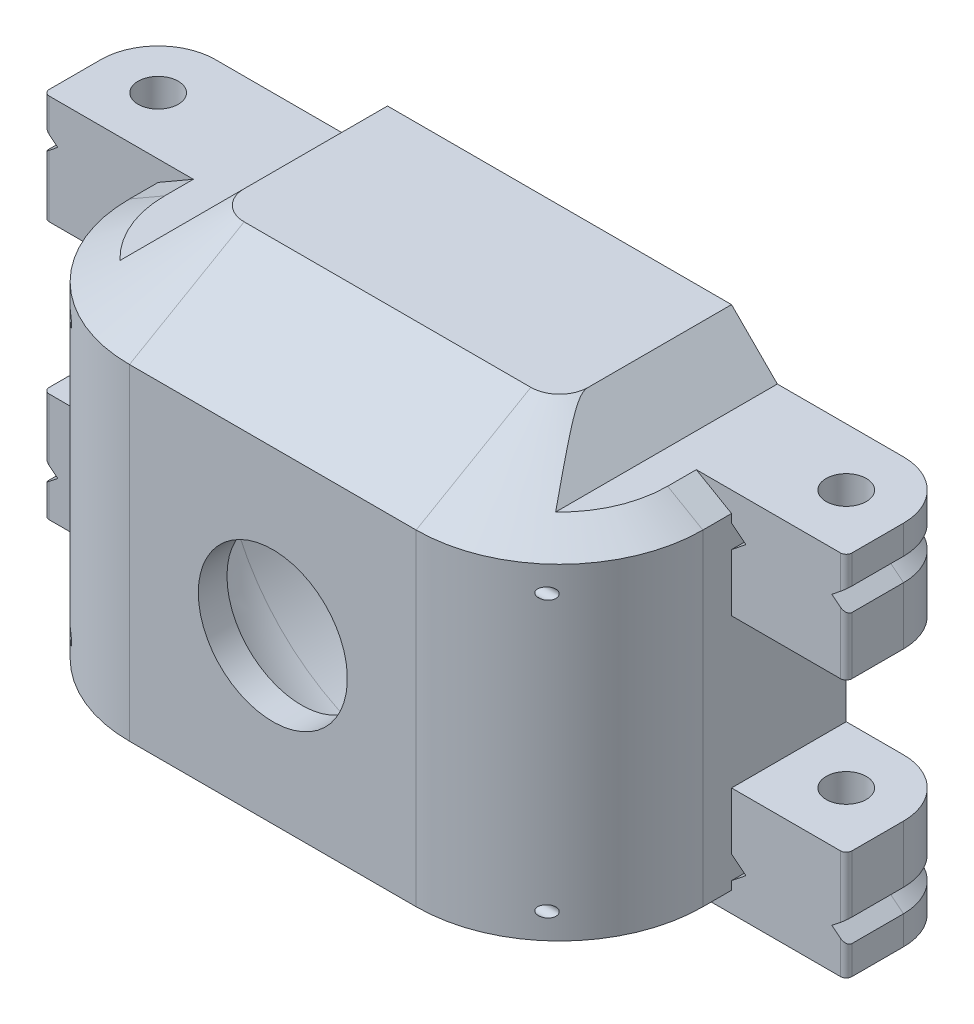
SolidWorks part; units mm, degrees
ref_plane "Front Plane" through (0, 0, 0) normal (0, 0, 1) x (1, 0, 0)
ref_plane "Top Plane" through (0, 0, 0) normal (0, 1, 0) x (1, 0, 0)
ref_plane "Right Plane" through (0, 0, 0) normal (1, 0, 0) x (0, 0, -1)
sketch "Sketch3" plane through (0, 0, 0) normal (0, 1, 0) x (1, 0, 0)
  line L0 (-3.2653, 27.8512) -> (-3.2653, -14.7845) construction
  line L4 (21.7347, 5.6122) -> (21.7347, 3.1122)
  line L5 (21.7347, 15.6122) -> (26.7347, 15.6122)
  line L7 (21.7347, 5.6122) -> (31.2347, 5.6122)
  line L8 (31.7347, 10.6122) -> (31.7347, 6.1122)
  line L9 (-38.2653, 10.6122) -> (-38.2653, 6.1122)
  line L10 (-28.2653, 5.6122) -> (-37.7653, 5.6122)
  line L11 (-28.2653, 15.6122) -> (-33.2653, 15.6122)
  line L12 (-28.2653, 5.6122) -> (-28.2653, 3.1122)
  line L13 (21.7347, 5.6122) -> (21.7347, 15.6122) construction
  line L14 (-15.7653, -9.3878) -> (-3.2653, -9.3878)
  line L15 (9.2347, -9.3878) -> (-3.2653, -9.3878)
  line L16 (21.7347, 15.6122) -> (-3.2653, 15.6122)
  line L17 (-3.2653, 15.6122) -> (-28.2653, 15.6122)
  circle A0 centre (26.7347, 10.6122) radius 1.75
  arc A1 (26.7347, 15.6122) -> (31.7347, 10.6122) centre (26.7347, 10.6122) cw
  arc A2 (31.2347, 5.6122) -> (31.7347, 6.1122) centre (31.2347, 6.1122) ccw
  arc A3 (9.2347, -9.3878) -> (21.7347, 3.1122) centre (9.2347, 3.1122) ccw
  arc A4 (-15.7653, -9.3878) -> (-28.2653, 3.1122) centre (-15.7653, 3.1122) cw
  arc A5 (-37.7653, 5.6122) -> (-38.2653, 6.1122) centre (-37.7653, 6.1122) cw
  arc A6 (-33.2653, 15.6122) -> (-38.2653, 10.6122) centre (-33.2653, 10.6122) ccw
  circle A7 centre (-33.2653, 10.6122) radius 1.75
  point P0 (-3.2653, 15.6122)
  point P28 (-3.2653, -9.3878)
  dimension "D5" = 3.5
  dimension "D3" = 0.5
  dimension "D2" = 12.5
  dimension "D1" = 12.5
  dimension "D4" = 5
  dimension "D6" = 5
  dimension "D7" = 5
extrude "Boss-Extrude1" add sketch "Sketch3" along normal blind 40
sketch "Sketch4" plane through (0, 0, -15.6122) normal (0, 0, -1) x (-1, 0, 0)
  line L5 (3.2653, 0) -> (3.2653, 40) construction
  line L7 (-26.7347, 0) -> (33.2653, 0) construction
  line L10 (38.2653, 13.5) -> (28.2653, 13.5)
  line L11 (-31.7347, 26.5) -> (-21.7347, 26.5)
  line L12 (-31.7347, 26.5) -> (-31.7347, 13.5)
  line L13 (-31.7347, 13.5) -> (-21.7347, 13.5)
  line L14 (-21.7347, 26.5) -> (-21.7347, 13.5)
  line L15 (28.2653, 26.5) -> (28.2653, 13.5)
  line L16 (38.2653, 26.5) -> (28.2653, 26.5)
  line L17 (38.2653, 26.5) -> (38.2653, 13.5)
  line L18 (-26.7347, 40) -> (33.2653, 40) construction
  line L19 (-31.7347, 20) -> (38.2653, 20) construction
  dimension "D2" = 13
  dimension "D4" = 10
extrude "Cut-Extrude1" cut sketch "Sketch4" against normal blind 10
ref_axis "Axis1" through (-33.2653, 13.5, -10.6122) along (0, -1, 0)
ref_plane "Plane1" through (0, 0, -10.6122) normal (0, 0, 1) x (1, 0, 0)
sketch "Sketch7" plane through (0, 0, -10.6122) normal (0, 0, 1) x (1, 0, 0)
  line L0 (-33.2653, 6.5) -> (-38.2653, 6.5) construction
  line L5 (-38.2653, 6.5) -> (-37.0153, 7.5)
  line L6 (-37.0153, 7.5) -> (-38.2653, 8.5)
  line L7 (-38.2653, 6.5) -> (-38.2653, 8.5) construction
  line L8 (-38.2653, 13.5) -> (-38.2653, 0) construction
  line L9 (-38.2653, 8.5) -> (-33.2653, 8.5) construction
  line L11 (-33.2653, 8.5) -> (-33.2653, 6.5) construction
  line L16 (-35.7653, 8.5) -> (-35.7653, 6.5) construction
  line L21 (-38.2653, 8.5) -> (-35.7653, 6.5) construction
  line L22 (-38.2653, 6.5) -> (-35.7653, 8.5) construction
  line L23 (-37.0153, 7.5) -> (-37.0153, 8.5) construction
  line L24 (-37.0153, 8.5) -> (-38.2653, 6.5) construction
  line L25 (-37.0153, 7.5) -> (-37.0153, 7) construction
  line L26 (-38.2653, 8.5) -> (-37.0153, 7) construction
  line L29 (-38.2653, 8.5) -> (-38.2653, 6.5)
  line L30 (-28.2653, 13.5) -> (-37.7653, 13.5) construction
  dimension "D1" = 2
  dimension "D2" = 2.5
  dimension "D3" = 5
revolve "Cut-Revolve1" cut sketch "Sketch7" angle 180 about axis through (-33.2653, 13.5, -10.6122) along (0, -1, 0)
sketch "Sketch9" plane through (0, 0, -5.6122) normal (0, 0, 1) x (1, 0, 0)
  line L0 (-38.2653, 13.5) -> (-28.2653, 13.5) construction
  line L5 (-38.2653, 8.5) -> (-37.0153, 7.5)
  line L6 (-37.0153, 7.5) -> (-38.2653, 6.5)
  line L7 (-37.7653, 13.5) -> (-38.2653, 13.5) construction
  line L8 (-28.2653, 13.5) -> (-28.2653, 0) construction
  line L9 (-28.2653, 0) -> (-38.2653, 0) construction
  line L11 (-38.2653, 13.5) -> (-38.2653, 0) construction
  line L16 (-33.2653, 13.5) -> (-33.2653, 0) construction
  line L21 (-38.2653, 6.5) -> (-38.2653, 8.5)
  line L22 (-28.2653, 6.5) -> (-28.2653, 8.5)
  line L33 (-38.2653, 6.5) -> (-33.2653, 6.5) construction
  line L34 (-35.7653, 6.5) -> (-35.7653, 0) construction
  line L35 (-33.2653, 8.5) -> (-38.2653, 8.5) construction
  line L36 (-38.2653, 8.5) -> (-33.2653, 6.5) construction
  line L37 (-38.2653, 6.5) -> (-33.2653, 8.5) construction
  line L38 (-35.7653, 7.5) -> (-35.7653, 8.5) construction
  line L39 (-35.7653, 7.5) -> (-35.7653, 6.5) construction
  line L40 (-35.7653, 8.5) -> (-38.2653, 6.5) construction
  line L41 (-35.7653, 6.5) -> (-38.2653, 8.5) construction
  line L48 (-37.0153, 7.5) -> (-37.0153, 8.5) construction
  line L49 (-37.0153, 7.5) -> (-37.0153, 6.5) construction
  line L50 (-38.2653, 6.5) -> (-37.0153, 8.5) construction
  line L51 (-38.2653, 8.5) -> (-37.0153, 6.5) construction
  line L52 (-38.2653, 8.5) -> (-37.6403, 7.5) construction
  line L53 (-37.6403, 7.5) -> (-38.2653, 6.5) construction
  line L54 (-38.2653, 6.5) -> (-38.2653, 8.5) construction
  line L58 (-28.2653, 8.5) -> (-29.5153, 7.5)
  line L59 (-29.5153, 7.5) -> (-28.2653, 6.5)
  dimension "D1" = 5
  dimension "D2" = 2
sketch "Sketch10" plane through (-28.2653, 0, 0) normal (-1, 0, 0) x (0, 0, 1)
  line L0 (-5.6122, 13.5) -> (9.3878, 13.5) construction
  line L5 (-3.1122, 40) -> (9.3878, 40) construction
  line L6 (-3.1122, 40) -> (-3.1122, 0) construction
  line L7 (-3.1122, 0) -> (9.3878, 0) construction
  line L8 (9.3878, 40) -> (9.3878, 0) construction
  line L9 (9.3414, 8.5) -> (3.1378, 7.5) construction
  line L10 (-3.1122, 0) -> (9.3878, 13.5) construction
  line L11 (3.1378, 6.75) -> (3.1378, 13.5) construction
  line L12 (9.3878, 7.5) -> (3.1378, 8.5) construction
  line L13 (3.1378, 6.75) -> (3.1378, 0) construction
  line L14 (9.3878, 8.5) -> (3.1378, 8.5) construction
  line L15 (9.3878, 7.5) -> (-3.1122, 7.5) construction
  circle A0 centre (6.2396, 8) radius 0.5
  dimension "D1" = 5
  dimension "D2" = 1
extrude "Cut-Extrude3" cut sketch "Sketch10" against normal blind 40
ref_plane "Plane2" through (0, 20, 0) normal (0, 1, 0) x (1, 0, 0)
ref_plane "Plane3" through (-3.2653, 0, 0) normal (-1, 0, 0) x (0, 0, 1)
sketch "Sketch11" plane through (0, 0, -15.6122) normal (0, 0, -1) x (-1, 0, 0)
  line L0 (-26.7347, 0) -> (33.2653, 40) construction
  line L1 (33.2653, 0) -> (-26.7347, 40) construction
  circle A0 centre (3.2653, 20) radius 18
extrude "Cut-Extrude4" cut sketch "Sketch11" against normal blind 22.5
sketch "Sketch13" plane through (0, 0, 6.8878) normal (0, 0, -1) x (-1, 0, 0)
  circle A0 centre (3.2653, 20) radius 6.5
  dimension "D1" = 13
extrude "Cut-Extrude5" cut sketch "Sketch13" against normal blind 2.5 and the other way blind 1
fillet "Fillet2" radius 11 1 edges at (-21.2653, 20, 6.8878)
chamfer "Chamfer2" distance 10 angle 30 5 edges at (-28.2653, 40, -4.3622) (21.7347, 40, -4.3622) (-24.6041, 40, 5.7266) (18.0735, 40, 5.7266) (-3.2653, 40, 9.3878) first distance on face at (26.7347, 40, -8.8622)
chamfer "Chamfer3" distance 10 angle 30 5 edges at (-28.2653, 0, -4.3622) (21.7347, 0, -4.3622) (-24.6041, 0, 5.7266) (18.0735, 0, 5.7266) (-3.2653, 0, 9.3878) first distance on face at (-3.2653, 0, -5.0898)
sketch "Sketch14" plane through (0, 0, -15.6122) normal (0, 0, -1) x (-1, 0, 0)
  line L0 (3.2653, 20) -> (3.2653, 40) construction
  line L1 (-11.7347, 40) -> (18.2653, 40)
  line L2 (-26.7347, 40) -> (33.2653, 40) construction
  line L3 (18.2653, 40) -> (22.2608, 36)
  line L4 (22.2608, 36) -> (44.6102, 36)
  line L5 (44.6102, 36) -> (44.6102, 43.9388)
  line L6 (44.6102, 43.9388) -> (-38.0795, 43.9388)
  line L8 (3.2653, 20) -> (54.5439, 20) construction
  line L9 (3.2653, 20) -> (3.2653, 0) construction
  line L10 (44.6102, -3.9388) -> (-38.0795, -3.9388)
  line L11 (44.6102, 4) -> (44.6102, -3.9388)
  line L12 (22.2608, 4) -> (44.6102, 4)
  line L13 (18.2653, 0) -> (22.2608, 4)
  line L14 (-11.7347, 0) -> (18.2653, 0)
  line L16 (-38.0795, 4) -> (-38.0795, -3.9388)
  line L17 (-15.7302, 4) -> (-32.312, 4)
  line L18 (-11.7347, 0) -> (-15.7302, 4)
  line L19 (-38.0795, 36) -> (-38.0795, 43.9388)
  line L20 (-15.7302, 36) -> (-32.312, 36)
  line L21 (-11.7347, 40) -> (-15.7302, 36)
  line L22 (-38.0795, 36) -> (-38.0795, 4)
  line L23 (-32.312, 4) -> (-32.312, 36)
  line L24 (3.2653, 43.9388) -> (3.2653, 52.7169) construction
  line L25 (3.2653, -3.9388) -> (3.2653, -5.4052) construction
  dimension "D1" = 15
  dimension "D2" = 4
extrude "Cut-Extrude6" cut sketch "Sketch14" against normal blind 20
extrude "Cut-Extrude7" cut sketch "Sketch9" against normal blind 5
mirror "Mirror1" about plane through (0, 20, 0) normal (0, 1, 0) of "Cut-Extrude3", "Cut-Extrude7", "Cut-Revolve1"
mirror "Mirror2" about plane through (-3.2653, 0, 0) normal (-1, 0, 0) of "Mirror1"
